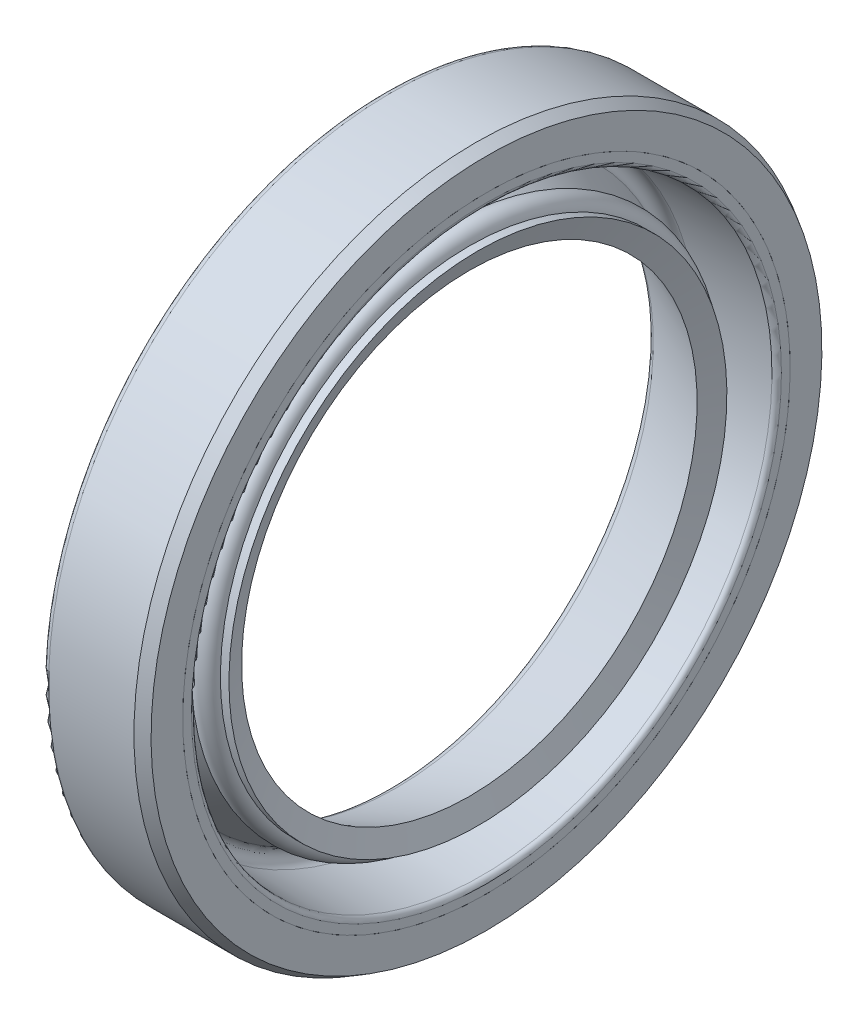
SolidWorks part; units mm, degrees
ref_plane "Front" through (0, 0, 0) normal (0, 0, 1) x (1, 0, 0)
ref_plane "Top" through (0, 0, 0) normal (0, 1, 0) x (1, 0, 0)
ref_plane "Right" through (0, 0, 0) normal (1, 0, 0) x (0, 0, -1)
sketch "Sketch1" plane through (0, 0, 0) normal (0, 0, 1) x (1, 0, 0)
  line L0 (1.6787, 35.8778) -> (11.9168, 31.75)
  line L1 (137.7714, 415.8994) -> (689.7714, 415.8994) construction
  line L2 (6.8429, 34.3958) -> (9.5335, 34.3958) construction
  line L3 (12.792, 47.625) -> (14.3002, 46.7542)
  line L4 (12.792, 47.625) -> (14.3002, 47.625) construction
  line L5 (14.3002, 47.625) -> (14.3002, 46.7542) construction
  line L6 (0, 38.3646) -> (4.7667, 38.3646) construction
  line L7 (6.8429, 39.6875) -> (4.7667, 39.6875) construction
  line L8 (4.7667, 39.6875) -> (4.7667, 37.0417) construction
  line L9 (2.3834, 42.5479) -> (2.3834, 38.9214) construction
  line L10 (6.8429, 37.0417) -> (4.7667, 37.0417) construction
  line L11 (3.5564, 38.9214) -> (2.3834, 38.9214) construction
  line L12 (3.0541, 37.8614) -> (8.5255, 35.2685)
  line L13 (11.9168, 42.5479) -> (11.9168, 31.75) construction
  line L14 (3.5155, 40.0938) -> (13.6533, 40.4478)
  line L15 (14.3002, 41.1177) -> (14.3002, 46.7542)
  line L16 (12.792, 47.625) -> (0.8938, 47.625)
  line L17 (0, 46.7312) -> (0, 38.3646)
  line L18 (14.3002, 0) -> (0, 0) construction
  line L19 (0, 31.75) -> (9.5335, 31.75) construction
  line L20 (6.8429, 47.625) -> (6.8429, 42.3333) construction
  line L21 (6.8429, 42.3333) -> (6.8429, 37.0417) construction
  line L22 (6.8429, 37.0417) -> (6.8429, 31.75) construction
  line L23 (9.5335, 37.0417) -> (9.5335, 31.75) construction
  line L24 (0, 42.5479) -> (4.7667, 42.5479) construction
  line L25 (4.7667, 42.5479) -> (9.5335, 42.5479) construction
  line L26 (9.5335, 42.5479) -> (14.3002, 42.5479) construction
  line L27 (9.5335, 37.0417) -> (9.5335, 42.5479) construction
  line L28 (87.5, 332.6365) -> (437.5, 332.6365) construction
  line L29 (4.7667, 39.6875) -> (4.7667, 41.1177) construction
  line L30 (4.7667, 41.1177) -> (4.7667, 42.5479) construction
  line L31 (4.7667, 41.1177) -> (14.3002, 41.1177) construction
  line L32 (13.6533, 40.4478) -> (0, 40.4478) construction
  line L33 (11.9168, 31.75) -> (13.1085, 34.7057)
  line L34 (11.9168, 37.149) -> (14.3002, 37.149) construction
  line L36 (13.1085, 34.7057) -> (11.9168, 34.7057)
  line L37 (0, 46.7312) -> (0.8938, 46.7312) construction
  line L38 (11.7562, 33.7375) -> (12.5638, 33.3547) construction
  line L39 (14.3002, 42.3333) -> (0, 42.3333)
  line L40 (13.1085, 37.149) -> (13.1085, 39.6875) construction
  line L41 (13.1085, 39.6875) -> (14.3002, 39.6875) construction
  line L42 (14.3002, 39.6875) -> (14.3002, 37.149) construction
  circle A0 centre (10.1408, 34.503) radius 1.7875 construction
  arc A1 (8.5255, 35.2685) -> (11.9168, 34.7057) centre (10.1408, 34.503) ccw
  arc A2 (0, 38.3646) -> (1.6787, 35.8778) centre (2.6813, 38.3646) ccw
  arc A3 (0.8938, 47.625) -> (0, 46.7312) centre (0.8938, 46.7312) ccw
  arc A7 (3.0541, 37.8614) -> (3.5155, 40.0938) centre (3.5564, 38.9214) cw
  arc A8 (13.6533, 40.4478) -> (14.3002, 41.1177) centre (13.6299, 41.1177) ccw
  dimension "D3" = 0.8938
  dimension "D1" = 2.6813
  dimension "D6" = 0.6703
  dimension "D7" = 1.1731
  dimension "D8" = 3.575
  dimension "D2" = 30
  dimension "D4" = 1.5082
  dimension "D5" = 2
revolve "Revolve1" add sketch "Sketch1" angle 360 about L18 region at (7.1077, 44.9529, 0) reverse direction yes
revolve "Revolve2" add sketch "Sketch1<3>" angle 360 about L18 region at (0.6064, 36.964, 0)
sketch "Sketch1<3>" plane through (0, 0, 0) normal (0, 0, 1) x (1, 0, 0) same geometry as "Sketch1"
sketch "Sketch2" plane through (0, 0, 0) normal (0, 0, 1) x (1, 0, 0)
  line L0 (0, 0) -> (14.3002, 0) construction
  circle A0 centre (10.1408, 34.503) radius 1.7875
  arc A1 (8.5255, 35.2685) -> (11.9168, 34.7057) centre (10.1408, 34.503) ccw construction
revolve "Revolve3" add sketch "Sketch2" angle 360 about L0
equation "\"D3@Sketch1\"=\"SealWidth@Sketch1\"*.0625"
equation "\"D4@Sketch1\"=\"D3@Sketch1\"*1.6875"
equation "\"D6@Sketch1\"=\"D3@Sketch1\"*.75"
equation "\"D1@Sketch1\"=\"D3@Sketch1\"*3"
equation "\"D7@Sketch1\"=\"D3@Sketch1\"*1.3125"
equation "\"D8@Sketch1\"=\"D3@Sketch1\"*4"
